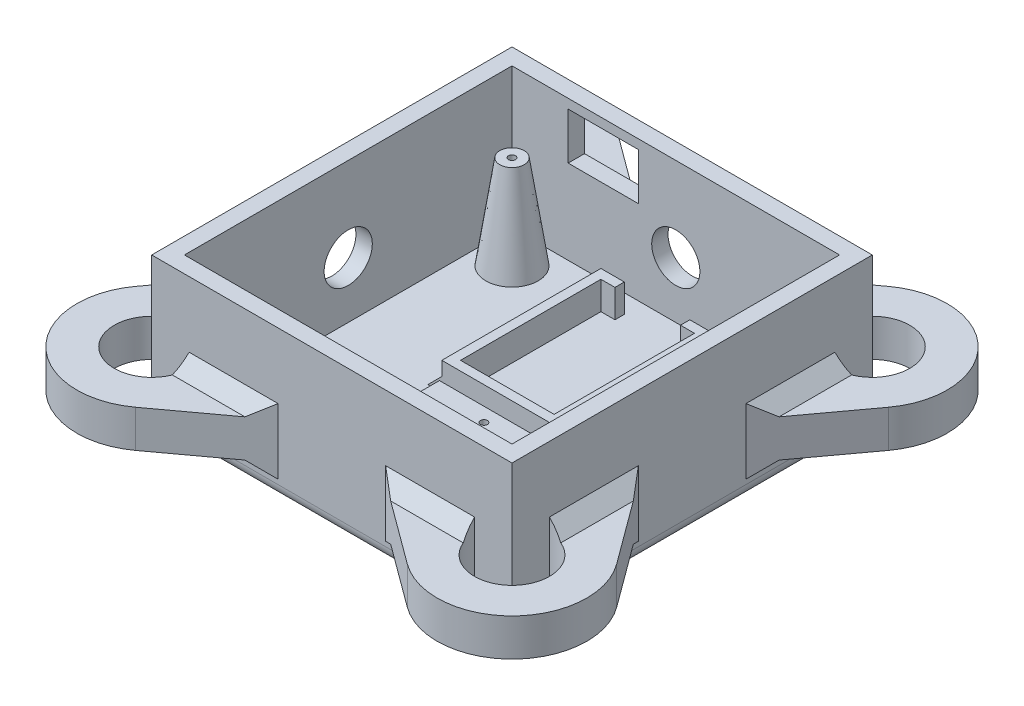
SolidWorks part; units mm, degrees
ref_plane "Front Plane" through (0, 0, 0) normal (0, 0, 1) x (1, 0, 0)
ref_plane "Top Plane" through (0, 0, 0) normal (0, 1, 0) x (1, 0, 0)
ref_plane "Right Plane" through (0, 0, 0) normal (1, 0, 0) x (0, 0, -1)
sketch "Sketch1" plane through (0, 0, 0) normal (0, 1, 0) x (1, 0, 0)
  line L0 (0, 38.5) -> (0, -38.5) construction
  line L2 (-35, 35) -> (35, 35)
  line L3 (35, 35) -> (35, -35)
  line L5 (-35, -35) -> (35, -35)
  line L6 (-35, 35) -> (-35, -35)
  line L7 (-38.5, 0) -> (38.5, 0) construction
  line L8 (38.5, 38.5) -> (-38.5, 38.5)
  line L9 (-38.5, 38.5) -> (-38.5, -38.5)
  line L11 (38.5, 38.5) -> (38.5, -38.5)
  line L12 (38.5, -38.5) -> (-38.5, -38.5)
  point P2 (35, 0)
  point P4 (0, 35)
  point P7 (0, 0)
  point P14 (0, 0)
  dimension "D1" = 70
  dimension "D2" = 77
  dimension "D3" = 77
  dimension "D4" = 70
extrude "Boss-Extrude1" add sketch "Sketch1" along normal blind 30 contours L6 L2 L3 L5 L12 L11 L8 L9 region at (37.4111, 0, 0)
sketch "Sketch2" plane through (0, 0, 0) normal (0, -1, 0) x (1, 0, 0)
  line L1 (-38.5, 38.5) -> (38.5, 38.5)
  line L2 (-38.5, 38.5) -> (-38.5, -38.5)
  line L3 (-38.5, -38.5) -> (38.5, -38.5)
  line L4 (38.5, 38.5) -> (38.5, -38.5)
extrude "Boss-Extrude2" add sketch "Sketch2" along normal blind 2
sketch "Sketch3" plane through (0, 0, 0) normal (0, 1, 0) x (1, 0, 0)
  line L0 (0, 35) -> (0, -35) construction
  line L1 (-35, 35) -> (35, 35) construction
  line L2 (-35, -35) -> (35, -35) construction
  line L3 (0, -35) -> (0, 0) construction
  line L4 (0, 0) -> (35, 0) construction
  line L5 (35, 35) -> (35, -35) construction
  line L6 (35, 0) -> (-35, 0) construction
  line L7 (-35, 35) -> (-35, -35) construction
  line L8 (-30, 30) -> (30, 30) construction
  line L9 (30, 30) -> (30, -30) construction
  line L10 (-30, -30) -> (30, -30) construction
  line L11 (-30, 30) -> (-30, -30) construction
  line L14 (-35, 35) -> (35, 35) construction
  circle A0 centre (28, 28) radius 2.6
  circle A1 centre (28, 28) radius 0.75
  circle A2 centre (28, -28) radius 2.6
  circle A3 centre (28, -28) radius 0.75
  circle A4 centre (-28, -28) radius 0.75
  circle A5 centre (-28, -28) radius 2.6
  circle A6 centre (-28, 28) radius 2.6
  circle A7 centre (-28, 28) radius 0.75
  point P23 (30, 0)
  point P28 (0, -30)
  point P32 (0, 30)
  dimension "D3" = 2
  dimension "D4" = 5.2
  dimension "D5" = 1.5
  dimension "D1" = 7
  dimension "D2" = 7
extrude "Boss-Extrude3" add sketch "Sketch3" along normal blind 20
ref_plane "Plane1" through (0, 5, 0) normal (0, -1, 0) x (-1, 0, 0)
sketch "Sketch11" plane through (0, 0, 0) normal (0, 1, 0) x (1, 0, 0)
  line L0 (12, -1.3684) -> (35, 0) construction
  line L1 (-10, 29) -> (-10, -1)
  line L3 (-12, 31) -> (-12, -3)
  line L5 (35, 35) -> (35, -35) construction
  line L6 (-35, 35) -> (35, 35) construction
  line L7 (-10, 29) -> (-7, 29)
  line L9 (-10, -1) -> (10, -1)
  line L12 (-12, -3) -> (12, -3)
  line L13 (12, -3) -> (12, 31)
  line L14 (12, 31) -> (7, 31)
  line L15 (7, 31) -> (7, 29)
  line L16 (10, 29) -> (10, -1)
  line L17 (0, -1) -> (10, -1)
  line L19 (7, 29) -> (10, 29)
  line L21 (-12, 31) -> (-7, 31)
  line L22 (-7, 31) -> (-7, 29)
  line L23 (-7, 29) -> (-10, 29)
  line L24 (7, 29) -> (10, 29)
  dimension "D1" = 30
  dimension "D2" = 6
  dimension "D3" = 10
  dimension "D4" = 2
  dimension "D5" = 10
  dimension "D6" = 2
  dimension "D7" = 3
  dimension "D8" = 3
  dimension "D9" = 2
  dimension "D10" = 2
  dimension "D11" = 2
fillet "Fillet1" radius 3 4 edges at (0, -2, 38.5) (38.5, -2, 0) (0, -2, -38.5) (-38.5, -2, 0)
extrude "Boss-Extrude8" add sketch "Sketch11" along normal blind 6 contours L22 L21 L3 L12 L13 L14 L15 L19 L16 L9 L1 L7 region at (-10.4162, 0, -14)
sketch "Sketch15" plane through (0, 0, -38.5) normal (0, 0, -1) x (-1, 0, 0)
  line L1 (0, 8.3) -> (0, -10.7) construction
  line L3 (-38.5, 30) -> (38.5, 30) construction
  circle A1 centre (0, 12) radius 5.15
  dimension "D1" = 18
  dimension "D2" = 10.3
extrude "Cut-Extrude2" cut sketch "Sketch15" against normal up to surface (3.5 mm away) up to face at (0, 15, -35)
sketch "Sketch17" plane through (0, 5, 0) normal (0, -1, 0) x (-1, 0, 0)
  line L0 (38.5, 22.5) -> (38.5, 11.5)
  line L1 (22.5, 38.5) -> (38.5, 38.5) construction
  line L2 (38.5, 38.5) -> (38.5, 22.5) construction
  line L3 (22.5, 38.5) -> (30.5, 38.5)
  line L4 (38.5, 30.5) -> (38.5, 22.5)
  line L5 (11.5, 38.5) -> (29.0185, 51.388)
  line L6 (-38.5, 38.5) -> (38.5, 38.5) construction
  line L7 (51.388, 29.0185) -> (38.5, 11.5)
  line L8 (38.5, 38.5) -> (38.5, -38.5) construction
  line L9 (11.5, 38.5) -> (22.5, 38.5)
  line L10 (0, 0) -> (0, -35.5) construction
  line L11 (-35.5, -35.5) -> (35.5, -35.5) construction
  line L12 (0, -35.5) -> (0, 0) construction
  line L13 (0, 0) -> (35.5, 0) construction
  line L14 (35.5, -35.5) -> (35.5, 35.5) construction
  line L15 (-38.5, 30.5) -> (-38.5, 22.5)
  line L16 (-22.5, 38.5) -> (-30.5, 38.5)
  line L17 (-11.5, 38.5) -> (-22.5, 38.5)
  line L18 (-11.5, 38.5) -> (-29.0185, 51.388)
  line L19 (-51.388, 29.0185) -> (-38.5, 11.5)
  line L20 (-38.5, 22.5) -> (-38.5, 11.5)
  line L21 (38.5, -30.5) -> (38.5, -22.5)
  line L22 (22.5, -38.5) -> (30.5, -38.5)
  line L23 (11.5, -38.5) -> (22.5, -38.5)
  line L24 (11.5, -38.5) -> (29.0185, -51.388)
  line L25 (51.388, -29.0185) -> (38.5, -11.5)
  line L26 (38.5, -22.5) -> (38.5, -11.5)
  line L27 (-22.5, -38.5) -> (-30.5, -38.5)
  line L28 (-11.5, -38.5) -> (-22.5, -38.5)
  line L29 (-11.5, -38.5) -> (-29.0185, -51.388)
  line L30 (-51.388, -29.0185) -> (-38.5, -11.5)
  line L31 (-38.5, -22.5) -> (-38.5, -11.5)
  line L32 (-38.5, -30.5) -> (-38.5, -22.5)
  arc A2 (38.5, 30.5) -> (30.5, 38.5) centre (38.5, 38.5) ccw
  arc A3 (51.388, 29.0185) -> (29.0185, 51.388) centre (38.5, 38.5) ccw
  arc A4 (-38.5, 30.5) -> (-30.5, 38.5) centre (-38.5, 38.5) cw
  arc A5 (-51.388, 29.0185) -> (-29.0185, 51.388) centre (-38.5, 38.5) cw
  arc A6 (38.5, -30.5) -> (30.5, -38.5) centre (38.5, -38.5) cw
  arc A7 (51.388, -29.0185) -> (29.0185, -51.388) centre (38.5, -38.5) cw
  arc A8 (-38.5, -30.5) -> (-30.5, -38.5) centre (-38.5, -38.5) ccw
  arc A9 (-51.388, -29.0185) -> (-29.0185, -51.388) centre (-38.5, -38.5) ccw
  dimension "D1" = 16
  dimension "D2" = 8
  dimension "D3" = 11
  dimension "D4" = 11
  dimension "D5" = 8
  dimension "D6" = 8
extrude "Boss-Extrude9" add sketch "Sketch17" against normal blind 8
chamfer "Chamfer1" distance 3 angle 45 16 edges at (-38.5, 5, -21) (-38.5, 13, -21) (-21, 13, -38.5) (-21, 5, -38.5) (21, 5, -38.5) (21, 13, -38.5) (38.5, 5, -21) (38.5, 13, -21) (38.5, 13, 21) (38.5, 5, 21) (21, 5, 38.5) (21, 13, 38.5) (-21, 13, 38.5) (-21, 5, 38.5) (-38.5, 5, 21) (-38.5, 13, 21)
chamfer "Chamfer2" distance 3 angle 45 2 edges at (-12, 0, -14) (12, 0, -14)
sketch "Sketch18" plane through (0, 0, 0) normal (0, 1, 0) x (1, 0, 0)
  line L0 (-35, -35) -> (35, -35) construction
  line L1 (-12.5, -35) -> (12.5, -35)
  line L2 (-12.5, -35) -> (-12.5, -3)
  line L3 (-12.5, -3) -> (12.5, -3)
  line L4 (12.5, -35) -> (12.5, -3)
  line L5 (-12.5, -35) -> (12.5, -3) construction
  line L6 (-12.5, -3) -> (12.5, -35) construction
  line L7 (-15, -3) -> (15, -3) construction
  line L13 (-12.5, -25) -> (12.5, -13) construction
  line L14 (-12.5, -13) -> (-9.433, -14.4721) construction
  point P0 (0, -19)
  point P5 (0, -35)
  point P11 (0, -19)
  line M5 (15, -3) -> (-15, -3)
  line M23 (-35, -35) -> (35, -35)
  dimension "D1" = 25
extrude "Boss-Extrude10" add sketch "Sketch18" along normal blind 2 contours L4 L2 M23 M5 region at (0, 0, 19)
sketch "Sketch19" plane through (0, 2, 0) normal (0, 1, 0) x (1, 0, 0)
  line L0 (12.5, -3) -> (-12.5, -3) construction
  line L1 (-12.5, -35) -> (12.5, -35) construction
  circle A0 centre (0, -6) radius 0.75
  circle A1 centre (0, -32) radius 0.75
  dimension "D1" = 1.5
  dimension "D2" = 3
  dimension "D3" = 3
extrude "Cut-Extrude3" cut sketch "Sketch19" against normal through all
sketch "Sketch20" plane through (-38.5, 0, 0) normal (-1, 0, 0) x (0, 0, 1)
  line L0 (-38.5, 30) -> (38.5, 30) construction
  circle A0 centre (0, 12) radius 5.15
  dimension "D1" = 10.3
  dimension "D2" = 18
extrude "Cut-Extrude4" cut sketch "Sketch20" against normal up to surface (3.5 mm away) up to face at (-35, 15, 0)
chamfer "Chamfer3" distance 3 distance2 20 4 edges at (28, 0, 25.4) (-28, 0, 25.4) (28, 0, -30.6) (-28, 0, -30.6) first distance on face at (28, 0, -30.6)
sketch "Sketch21" plane through (0, 0, -35) normal (0, 0, 1) x (1, 0, 0)
  line L1 (-23, 18) -> (-8, 18)
  line L2 (-23, 18) -> (-23, 28)
  line L3 (-23, 28) -> (-8, 28)
  line L4 (-8, 18) -> (-8, 28)
  line L5 (-23, 18) -> (-8, 28) construction
  line L6 (-23, 28) -> (-8, 18) construction
  line L8 (-35, 30) -> (-35, 0) construction
  line L10 (-25.4, 20) -> (-30.6, 20) construction
  point P0 (-15.5, 23)
  dimension "D1" = 19.5
  dimension "D2" = 10
  dimension "D3" = 15
  dimension "D4" = 3
extrude "Cut-Extrude5" cut sketch "Sketch21" against normal up to surface (3.5 mm away) up to face at (21, 9, -38.5)
